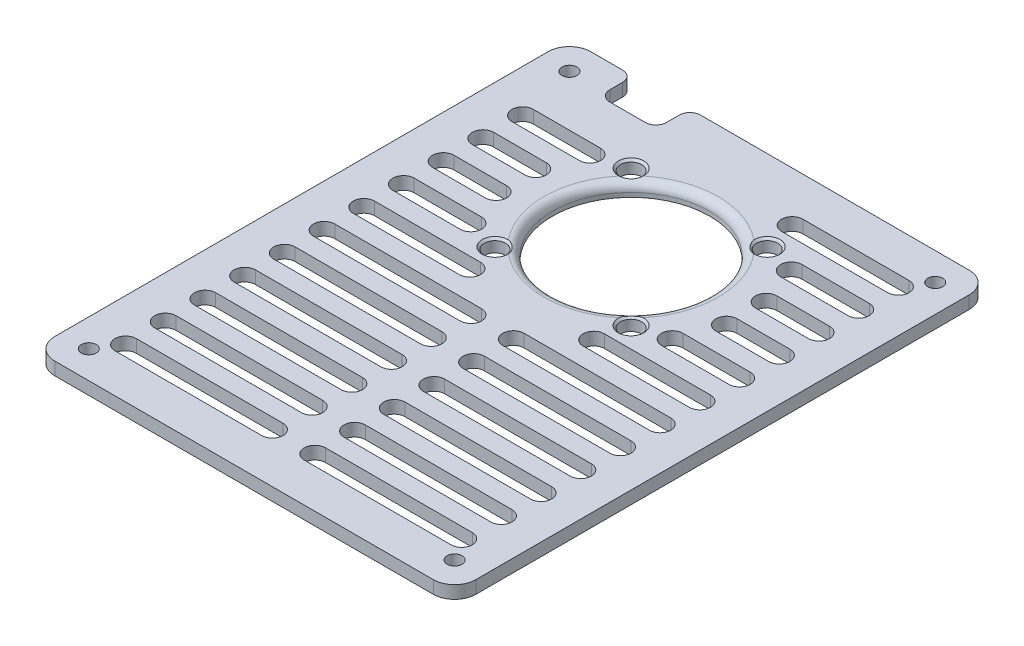
SolidWorks part; units mm, degrees
material "Hot Galvanized Steel"
ref_plane "Front" through (0, 0, 0) normal (0, 0, 1) x (1, 0, 0)
ref_plane "Top" through (0, 0, 0) normal (0, 1, 0) x (1, 0, 0)
ref_plane "Right" through (0, 0, 0) normal (1, 0, 0) x (0, 0, -1)
sketch "Sketch1" plane through (0, 0, 0) normal (0, 1, 0) x (1, 0, 0)
  line L1 (-49.5, 63) -> (49.5, 63)
  line L2 (-49.5, 63) -> (-49.5, -63)
  line L3 (-49.5, -63) -> (49.5, -63)
  line L4 (49.5, 63) -> (49.5, -63)
  line L5 (-49.5, 63) -> (49.5, -63) construction
  line L6 (-49.5, -63) -> (49.5, 63) construction
  point P0 (0, 0)
  dimension "D1" = 99
  dimension "D2" = 126
extrude "Boss-Extrude1" add sketch "Sketch1" along normal blind 3
fillet "Fillet1" radius 5 4 edges at (49.5, 1.5, 63) (-49.5, 1.5, 63) (49.5, 1.5, -63) (-49.5, 1.5, -63)
sketch "Sketch5" plane through (0, 3, 0) normal (0, 1, 0) x (1, 0, 0)
  line L0 (44.5, 63) -> (-44.5, 63) construction
  line L2 (0, 46.5) -> (0, 28) construction
  line L3 (0, 28) -> (18.5, 28) construction
  circle A0 centre (0, 28) radius 18.5
  circle A1 centre (16, 44) radius 2.5
  circle A2 centre (16, 12) radius 2.5
  circle A3 centre (-16, 12) radius 2.5
  circle A4 centre (-16, 44) radius 2.5
  dimension "D1" = 37
  dimension "D4" = 32
  dimension "D6" = 5
  dimension "D2" = 35
  dimension "D5" = 32
extrude "Cut-Extrude4" cut sketch "Sketch5" against normal through all
sketch "Sketch2" plane through (0, 3, 0) normal (0, 1, 0) x (1, 0, 0)
  line L0 (0, 63) -> (0, 0) construction
  line L1 (44.5, 63) -> (-44.5, 63) construction
  line L2 (0, 0) -> (49.5, 0) construction
  line L3 (49.5, -58) -> (49.5, 58) construction
  circle A0 centre (-43, 56.5) radius 1.75
  circle A1 centre (43, 56.5) radius 1.75
  circle A2 centre (43, -56.5) radius 1.75
  circle A3 centre (-43, -56.5) radius 1.75
  dimension "D1" = 3.5
  dimension "D2" = 86
  dimension "D3" = 113
extrude "Cut-Extrude1" cut sketch "Sketch2" against normal through all
chamfer "Chamfer1" distance 0.5 angle 45 4 edges at (-16, 3, -46.5) (16, 3, -41.5) (16, 3, -14.5) (-16, 3, -9.5)
fillet "Fillet3" radius 2 1 edges at (0, 3, -9.5)
sketch "Sketch4" plane through (0, 3, 0) normal (0, 1, 0) x (1, 0, 0)
  line L0 (0, 63) -> (0, -63) construction
  line L1 (-39.5, -51.3333) -> (-39.5, -42) construction
  line L2 (-44.5, -63) -> (44.5, -63) construction
  line L3 (-39.5, -51.3333) -> (-5, -51.3333) construction
  line L4 (-39.5, -48.8333) -> (-5, -48.8333)
  line L5 (-39.5, -53.8333) -> (-5, -53.8333)
  line L6 (-39.5, -42) -> (-5, -42) construction
  line L7 (-39.5, -39.5) -> (-5, -39.5)
  line L8 (-39.5, -44.5) -> (-5, -44.5)
  line L9 (-39.5, -32.6667) -> (-5, -32.6667) construction
  line L10 (-39.5, -30.1667) -> (-5, -30.1667)
  line L11 (-39.5, -35.1667) -> (-5, -35.1667)
  line L12 (-39.5, -23.3333) -> (-5, -23.3333) construction
  line L13 (-39.5, -20.8333) -> (-5, -20.8333)
  line L14 (-39.5, -25.8333) -> (-5, -25.8333)
  line L15 (-39.5, -14) -> (-5, -14) construction
  line L16 (-39.5, -11.5) -> (-5, -11.5)
  line L17 (-39.5, -16.5) -> (-5, -16.5)
  line L18 (-39.5, -4.6667) -> (-5, -4.6667) construction
  line L19 (-39.5, -2.1667) -> (-5, -2.1667)
  line L20 (-39.5, -7.1667) -> (-5, -7.1667)
  line L21 (-39.5, 4.6667) -> (-14.5535, 4.6667) construction
  line L22 (-39.5, 7.1667) -> (-14.5535, 7.1667)
  line L23 (-39.5, 2.1667) -> (-14.5535, 2.1667)
  line L24 (-39.5, 14) -> (-23.6696, 14) construction
  line L25 (-39.5, 16.5) -> (-23.6696, 16.5)
  line L26 (-39.5, 11.5) -> (-23.6696, 11.5)
  line L27 (-39.5, 23.3333) -> (-27.1011, 23.3333) construction
  line L28 (-39.5, 25.8333) -> (-27.1011, 25.8333)
  line L29 (-39.5, 20.8333) -> (-27.1011, 20.8333)
  line L30 (-39.5, 32.6667) -> (-27.1011, 32.6667) construction
  line L31 (-39.5, 35.1667) -> (-27.1011, 35.1667)
  line L32 (-39.5, 30.1667) -> (-27.1011, 30.1667)
  line L33 (-39.5, 42) -> (-23.6696, 42) construction
  line L34 (-39.5, -42) -> (-39.5, -32.6667) construction
  line L35 (-39.5, -32.6667) -> (-39.5, -23.3333) construction
  line L38 (-39.5, -23.3333) -> (-39.5, -14) construction
  line L41 (-39.5, -14) -> (-39.5, -4.6667) construction
  line L44 (-39.5, -4.6667) -> (-39.5, 4.6667) construction
  line L47 (-39.5, 4.6667) -> (-39.5, 14) construction
  line L50 (-39.5, 14) -> (-39.5, 23.3333) construction
  line L53 (-39.5, 23.3333) -> (-39.5, 32.6667) construction
  line L56 (-39.5, 32.6667) -> (-39.5, 42) construction
  line L59 (0, 28) -> (-39.5, 28) construction
  line L62 (39.5, 42) -> (23.6696, 42) construction
  line L65 (-49.5, 58) -> (-49.5, -58) construction
  line L66 (39.5, 44.5) -> (23.6696, 44.5)
  line L69 (39.5, 39.5) -> (23.6696, 39.5)
  line L72 (39.5, 32.6667) -> (27.1011, 32.6667) construction
  line L73 (-39.5, 44.5) -> (-23.6696, 44.5)
  line L76 (-39.5, 39.5) -> (-23.6696, 39.5)
  line L79 (39.5, 35.1667) -> (27.1011, 35.1667)
  line L80 (39.5, 30.1667) -> (27.1011, 30.1667)
  line L81 (39.5, 23.3333) -> (27.1011, 23.3333) construction
  line L82 (44.5, 63) -> (-44.5, 63) construction
  line L83 (39.5, 25.8333) -> (27.1011, 25.8333)
  line L84 (39.5, 20.8333) -> (27.1011, 20.8333)
  line L85 (39.5, 14) -> (23.6696, 14) construction
  line L86 (39.5, 16.5) -> (23.6696, 16.5)
  line L87 (39.5, 11.5) -> (23.6696, 11.5)
  line L88 (39.5, 4.6667) -> (14.5535, 4.6667) construction
  line L89 (39.5, 7.1667) -> (14.5535, 7.1667)
  line L90 (39.5, 2.1667) -> (14.5535, 2.1667)
  line L91 (39.5, -4.6667) -> (5, -4.6667) construction
  line L92 (39.5, -2.1667) -> (5, -2.1667)
  line L93 (39.5, -7.1667) -> (5, -7.1667)
  line L94 (39.5, -14) -> (5, -14) construction
  line L95 (39.5, -11.5) -> (5, -11.5)
  line L96 (39.5, -16.5) -> (5, -16.5)
  line L97 (39.5, -23.3333) -> (5, -23.3333) construction
  line L98 (39.5, -20.8333) -> (5, -20.8333)
  line L99 (39.5, -25.8333) -> (5, -25.8333)
  line L100 (39.5, -32.6667) -> (5, -32.6667) construction
  line L101 (39.5, -30.1667) -> (5, -30.1667)
  line L102 (39.5, -35.1667) -> (5, -35.1667)
  line L103 (39.5, -42) -> (5, -42) construction
  line L104 (39.5, -39.5) -> (5, -39.5)
  line L105 (39.5, -44.5) -> (5, -44.5)
  line L106 (39.5, -51.3333) -> (5, -51.3333) construction
  line L107 (39.5, -48.8333) -> (5, -48.8333)
  line L108 (39.5, -53.8333) -> (5, -53.8333)
  line L109 (14.5535, 51.3333) -> (39.5, 51.3333) construction
  line L110 (14.5535, 53.8333) -> (39.5, 53.8333)
  line L111 (14.5535, 48.8333) -> (39.5, 48.8333)
  line L112 (39.5, -51.3333) -> (39.5, -63) construction
  line L113 (39.5, 51.3333) -> (39.5, 63) construction
  line L114 (39.5, 51.3333) -> (39.5, 42) construction
  arc A0 (-39.5, -48.8333) -> (-39.5, -53.8333) centre (-39.5, -51.3333) ccw
  arc A1 (-5, -53.8333) -> (-5, -48.8333) centre (-5, -51.3333) ccw
  arc A2 (-39.5, -39.5) -> (-39.5, -44.5) centre (-39.5, -42) ccw
  arc A3 (-5, -44.5) -> (-5, -39.5) centre (-5, -42) ccw
  arc A4 (-39.5, -30.1667) -> (-39.5, -35.1667) centre (-39.5, -32.6667) ccw
  arc A5 (-5, -35.1667) -> (-5, -30.1667) centre (-5, -32.6667) ccw
  arc A6 (-39.5, -20.8333) -> (-39.5, -25.8333) centre (-39.5, -23.3333) ccw
  arc A7 (-5, -25.8333) -> (-5, -20.8333) centre (-5, -23.3333) ccw
  arc A8 (-39.5, -11.5) -> (-39.5, -16.5) centre (-39.5, -14) ccw
  arc A9 (-5, -16.5) -> (-5, -11.5) centre (-5, -14) ccw
  arc A10 (-39.5, -2.1667) -> (-39.5, -7.1667) centre (-39.5, -4.6667) ccw
  arc A11 (-5, -7.1667) -> (-5, -2.1667) centre (-5, -4.6667) ccw
  arc A12 (-39.5, 7.1667) -> (-39.5, 2.1667) centre (-39.5, 4.6667) ccw
  arc A13 (-14.5535, 2.1667) -> (-14.5535, 7.1667) centre (-14.5535, 4.6667) ccw
  arc A14 (-39.5, 16.5) -> (-39.5, 11.5) centre (-39.5, 14) ccw
  arc A15 (-23.6696, 11.5) -> (-23.6696, 16.5) centre (-23.6696, 14) ccw
  arc A16 (-39.5, 25.8333) -> (-39.5, 20.8333) centre (-39.5, 23.3333) ccw
  arc A17 (-27.1011, 20.8333) -> (-27.1011, 25.8333) centre (-27.1011, 23.3333) ccw
  arc A18 (-39.5, 35.1667) -> (-39.5, 30.1667) centre (-39.5, 32.6667) ccw
  arc A19 (-27.1011, 30.1667) -> (-27.1011, 35.1667) centre (-27.1011, 32.6667) ccw
  arc A48 (-39.5, 44.5) -> (-39.5, 39.5) centre (-39.5, 42) ccw
  arc A49 (-23.6696, 39.5) -> (-23.6696, 44.5) centre (-23.6696, 42) ccw
  circle A50 centre (0, 28) radius 27.5 construction
  arc A51 (39.5, 44.5) -> (39.5, 39.5) centre (39.5, 42) cw
  arc A52 (23.6696, 39.5) -> (23.6696, 44.5) centre (23.6696, 42) cw
  arc A53 (39.5, 35.1667) -> (39.5, 30.1667) centre (39.5, 32.6667) cw
  arc A54 (27.1011, 30.1667) -> (27.1011, 35.1667) centre (27.1011, 32.6667) cw
  arc A55 (39.5, 25.8333) -> (39.5, 20.8333) centre (39.5, 23.3333) cw
  arc A56 (27.1011, 20.8333) -> (27.1011, 25.8333) centre (27.1011, 23.3333) cw
  arc A57 (39.5, 16.5) -> (39.5, 11.5) centre (39.5, 14) cw
  arc A58 (23.6696, 11.5) -> (23.6696, 16.5) centre (23.6696, 14) cw
  arc A59 (39.5, 7.1667) -> (39.5, 2.1667) centre (39.5, 4.6667) cw
  arc A60 (14.5535, 2.1667) -> (14.5535, 7.1667) centre (14.5535, 4.6667) cw
  arc A61 (39.5, -2.1667) -> (39.5, -7.1667) centre (39.5, -4.6667) cw
  arc A62 (5, -7.1667) -> (5, -2.1667) centre (5, -4.6667) cw
  arc A63 (39.5, -11.5) -> (39.5, -16.5) centre (39.5, -14) cw
  arc A64 (5, -16.5) -> (5, -11.5) centre (5, -14) cw
  arc A65 (39.5, -20.8333) -> (39.5, -25.8333) centre (39.5, -23.3333) cw
  arc A66 (5, -25.8333) -> (5, -20.8333) centre (5, -23.3333) cw
  arc A67 (39.5, -30.1667) -> (39.5, -35.1667) centre (39.5, -32.6667) cw
  arc A68 (5, -35.1667) -> (5, -30.1667) centre (5, -32.6667) cw
  arc A69 (39.5, -39.5) -> (39.5, -44.5) centre (39.5, -42) cw
  arc A70 (5, -44.5) -> (5, -39.5) centre (5, -42) cw
  arc A71 (39.5, -48.8333) -> (39.5, -53.8333) centre (39.5, -51.3333) cw
  arc A72 (5, -53.8333) -> (5, -48.8333) centre (5, -51.3333) cw
  arc A73 (14.5535, 53.8333) -> (14.5535, 48.8333) centre (14.5535, 51.3333) ccw
  arc A74 (39.5, 48.8333) -> (39.5, 53.8333) centre (39.5, 51.3333) ccw
  point P8 (-22.25, -51.3333)
  point P16 (-22.25, -42)
  point P23 (-22.25, -32.6667)
  point P30 (-22.25, -23.3333)
  point P37 (-22.25, -14)
  point P44 (-22.25, -4.6667)
  point P51 (-27.0268, 4.6667)
  point P58 (-31.5848, 14)
  point P65 (-33.3006, 23.3333)
  point P72 (-33.3006, 32.6667)
  point P86 (27.0268, 51.3333)
  point P94 (31.5848, 42)
  point P101 (33.3006, 32.6667)
  point P108 (33.3006, 23.3333)
  point P115 (31.5848, 14)
  point P122 (27.0268, 4.6667)
  point P129 (22.25, -4.6667)
  point P136 (22.25, -14)
  point P143 (22.25, -23.3333)
  point P153 (22.25, -32.6667)
  point P160 (22.25, -42)
  point P168 (-31.5848, 42)
  point P173 (22.25, -51.3333)
  dimension "D4" = 55
  dimension "D1" = 5
  dimension "D5" = 10
  dimension "D2" = 5
extrude "Cut-Extrude3" cut sketch "Sketch4" against normal through all
sketch "Sketch3" plane through (0, 3, 0) normal (0, 1, 0) x (1, 0, 0)
  line L1 (-34.5, 63) -> (-21.1696, 63)
  line L2 (-34.5, 63) -> (-34.5, 55)
  line L3 (-34.5, 55) -> (-21.1696, 55)
  line L4 (-21.1696, 63) -> (-21.1696, 55)
  line L6 (44.5, 63) -> (-44.5, 63) construction
  line L7 (-49.5, 58) -> (-49.5, -58) construction
  arc A2 (-23.6696, 39.5) -> (-23.6696, 44.5) centre (-23.6696, 42) ccw construction
  dimension "D1" = 15
  dimension "D4" = 8
extrude "Cut-Extrude2" cut sketch "Sketch3" against normal through all
fillet "Fillet2" radius 2.5 4 edges at (-34.5, 1.5, -55) (-21.1696, 1.5, -55) (-21.1696, 1.5, -63) (-34.5, 1.5, -63)
